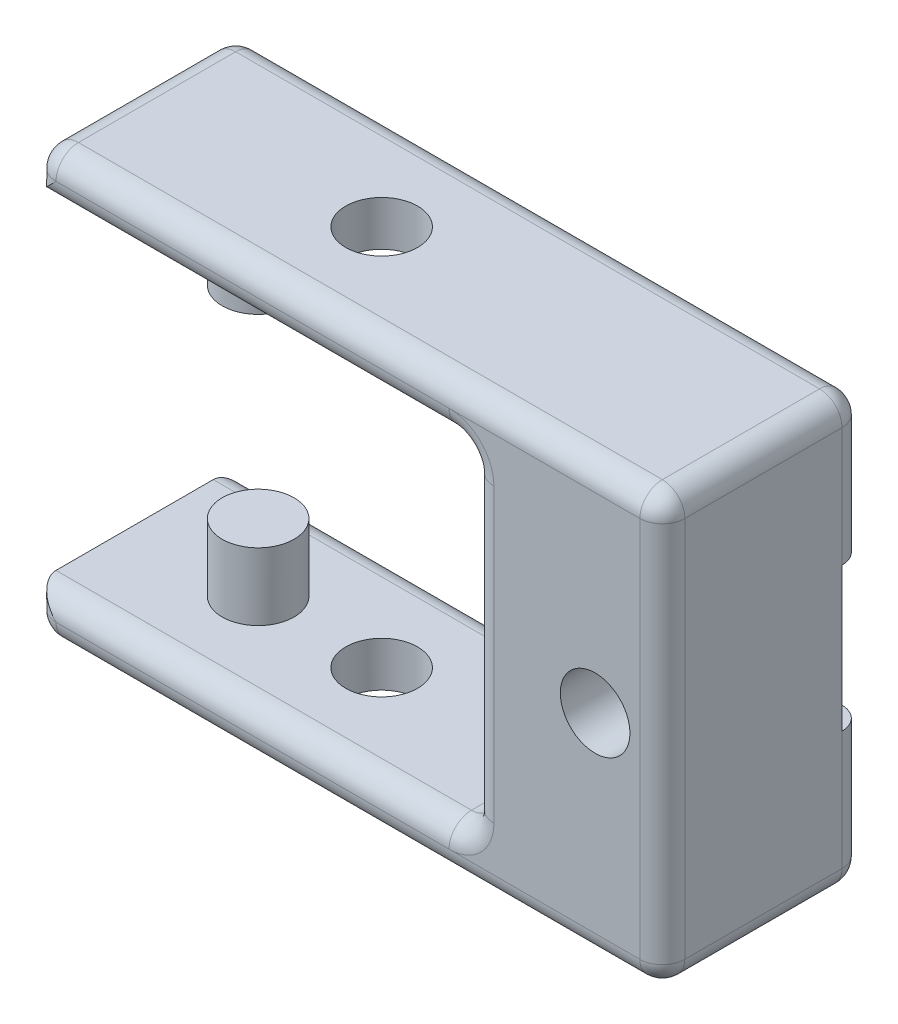
SolidWorks part; units mm, degrees
ref_plane "Plane Front" through (0, 0, 0) normal (0, 0, 1) x (1, 0, 0)
ref_plane "Plane Top" through (0, 0, 0) normal (0, 1, 0) x (1, 0, 0)
ref_plane "Plane Right" through (0, 0, 0) normal (1, 0, 0) x (0, 0, -1)
sketch "Sketch1" plane through (0, 0, 0) normal (0, 1, 0) x (1, 0, 0)
  line L1 (-11.6329, 5.2514) -> (16.3671, 5.2514)
  line L2 (-11.6329, 5.2514) -> (-11.6329, -3.7486)
  line L3 (-11.6329, -3.7486) -> (16.3671, -3.7486)
  line L4 (16.3671, 5.2514) -> (16.3671, -3.7486)
  dimension "D1" = 28
  dimension "D2" = 9
extrude "Extrude1" add sketch "Sketch1" along normal blind 19
sketch "Sketch2" plane through (0, 19, 0) normal (0, 1, 0) x (1, 0, 0)
  line L0 (-11.6329, 5.2514) -> (-11.6329, -3.7486) construction
  line L1 (16.3671, 5.2514) -> (-11.6329, 5.2514) construction
  circle A0 centre (-0.6329, 0.7514) radius 1.6
  dimension "D1" = 3.2
  dimension "D2" = 11
  dimension "D3" = 4.5
extrude "Extrude2" cut sketch "Sketch2" against normal through all
sketch "Sketch3" plane through (0, 0, 3.7486) normal (0, 0, 1) x (1, 0, 0)
  line L5 (-11.6329, 19) -> (16.3671, 19) construction
  line L6 (-11.6329, 17) -> (7.8671, 17)
  line L7 (-11.6329, 17) -> (-11.6329, 2)
  line L8 (-11.6329, 2) -> (7.8671, 2)
  line L9 (7.8671, 17) -> (7.8671, 2)
  line L10 (-11.6329, 0) -> (16.3671, 0) construction
  line L11 (-11.6329, 19) -> (-11.6329, 0) construction
  dimension "D1" = 19.5
  dimension "D2" = 15
  dimension "D3" = 2
  dimension "D4" = 2
  dimension "D5" = 0
extrude "Extrude3" cut sketch "Sketch3" against normal through all
sketch "Sketch6" plane through (0, 2, 0) normal (0, 1, 0) x (1, 0, 0)
  line L2 (-11.6329, 5.2514) -> (7.8671, 5.2514) construction
  line L3 (-11.6329, 5.2514) -> (-11.6329, -3.7486) construction
  circle A0 centre (-6.1329, 0.7514) radius 1.6
  dimension "D1" = 3.2
  dimension "D2" = 4.5
  dimension "D3" = 5.5
extrude "Extrude4" add sketch "Sketch6" along direction (0, -1, 0) on the side of the normal blind 3
sketch "Sketch7" plane through (0, 17, 0) normal (0, -1, 0) x (1, 0, 0)
  line L0 (7.8671, 3.7486) -> (-11.6329, 3.7486) construction
  line L1 (-11.6329, -5.2514) -> (-11.6329, 3.7486) construction
  circle A0 centre (-6.1329, -0.7514) radius 1.6
  dimension "D1" = 3.2
  dimension "D2" = 4.5
  dimension "D3" = 5.5
extrude "Extrude5" add sketch "Sketch7" along normal blind 3
sketch "Sketch8" plane through (0, 0, -5.2514) normal (0, 0, -1) x (-1, 0, 0)
  line L0 (-11.4258, 19) -> (-11.4258, 0) construction
  line L1 (-16.3671, 19) -> (11.6329, 19) construction
  line L2 (-16.3671, 0) -> (11.6329, 0) construction
  line L3 (-16.3671, 19) -> (-16.3671, 0) construction
  line L4 (-16.3671, 12.7) -> (-9.7671, 12.7)
  line L5 (-16.3671, 12.7) -> (-16.3671, 6.3)
  line L6 (-16.3671, 6.3) -> (-9.7671, 6.3)
  line L7 (-9.7671, 12.7) -> (-9.7671, 6.3)
  point P12 (-11.4258, 9.5)
  point P13 (-13.0671, 6.3)
  dimension "D1" = 3.2
  dimension "D2" = 3.2
  dimension "D3" = 6.6
extrude "Extrude6" cut sketch "Sketch8" against normal blind 1
sketch "Sketch9" plane through (0, 0, -4.2514) normal (0, 0, -1) x (-1, 0, 0)
  line L0 (-16.3671, 12.7) -> (-16.3671, 6.3) construction
  line L1 (-9.7671, 12.7) -> (-16.3671, 12.7) construction
  circle A0 centre (-13.3731, 9.5) radius 1.55
  dimension "D1" = 2.994
  dimension "D3" = 3.1
  dimension "D2" = 3.2
extrude "Extrude7" cut sketch "Sketch9" against normal through all
fillet "Fillet1" radius 1 23 edges at (2.3671, 19, -5.2514) (2.3671, 0, 3.7486) (2.3671, 0, -5.2514) (16.3671, 0, -0.7514) (16.3671, 3.15, -5.2514) (16.3671, 9.5, 3.7486) (-11.6329, 0, -0.7514) (-1.8829, 2, 3.7486) (-1.8829, 2, -5.2514) (7.8671, 2, -0.7514) (7.8671, 17, -0.7514) (7.8671, 9.5, -5.2514) (-1.8829, 17, -5.2514) (-11.6329, 19, -0.7514) (7.8671, 9.5, 3.7486) (-1.8829, 17, 3.7486) (2.3671, 19, 3.7486) (16.3671, 19, -0.7514) (16.3671, 15.85, -5.2514) (-11.6329, 1, -5.2514) (-11.6329, 1, 3.7486) (-11.6329, 18, -5.2514) (-11.6329, 18, 3.7486)
